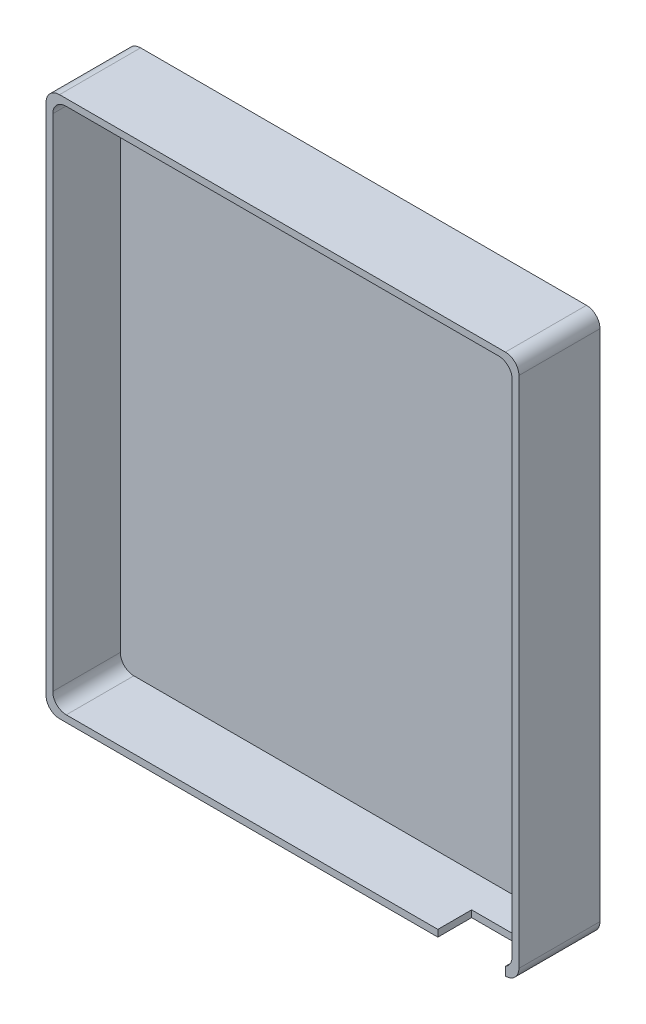
SolidWorks part; units mm, degrees
ref_plane "Front Plane" through (0, 0, 0) normal (0, 0, 1) x (1, 0, 0)
ref_plane "Top Plane" through (0, 0, 0) normal (0, 1, 0) x (1, 0, 0)
ref_plane "Right Plane" through (0, 0, 0) normal (1, 0, 0) x (0, 0, -1)
sketch "Sketch1" plane through (0, 0, 0) normal (0, 0, 1) x (1, 0, 0)
  line L0 (2.54, 0) -> (86.36, 0)
  line L1 (88.9, 2.54) -> (88.9, 99.06)
  line L2 (86.36, 101.6) -> (2.54, 101.6)
  line L3 (0, 99.06) -> (0, 2.54)
  line L8 (3.81, 1.27) -> (85.09, 1.27)
  line L9 (87.63, 3.81) -> (87.63, 97.79)
  line L10 (85.09, 100.33) -> (3.7414, 100.33)
  line L11 (1.27, 97.8586) -> (1.27, 3.81)
  arc A0 (2.54, 101.6) -> (0, 99.06) centre (2.54, 99.06) ccw
  arc A1 (88.9, 99.06) -> (86.36, 101.6) centre (86.36, 99.06) ccw
  arc A2 (86.36, 0) -> (88.9, 2.54) centre (86.36, 2.54) ccw
  arc A3 (0, 2.54) -> (2.54, 0) centre (2.54, 2.54) ccw
  arc A4 (1.27, 3.81) -> (3.81, 1.27) centre (3.81, 3.81) ccw
  arc A5 (85.09, 1.27) -> (87.63, 3.81) centre (85.09, 3.81) ccw
  arc A6 (87.63, 97.79) -> (85.09, 100.33) centre (85.09, 97.79) ccw
  arc A7 (1.27, 97.8586) -> (3.7414, 100.33) centre (3.7414, 97.8586) cw
  point P13 (0, 0)
  dimension "D1" = 2.54
  dimension "D2" = 2.54
  dimension "D3" = 2.54
  dimension "D4" = 2.54
  dimension "D5" = 2.54
  dimension "D6" = 2.54
  dimension "D7" = 2.54
  dimension "D8" = 2.4714
  dimension "D9" = 1.27
  dimension "D10" = 1.27
  dimension "D11" = 88.9
  dimension "D12" = 1.27
  dimension "D13" = 101.6
  dimension "D14" = 1.27
extrude "Boss-Extrude2" add sketch "Sketch1" along normal blind 2.54 contours A7 L11 A4 L8 A5 L9 A6 L10 region at (44.4496, 50.8004, 0)
extrude "Boss-Extrude3" add sketch "Sketch1<3>" along normal blind 15.24 contours L3 A3 L0 A2 L1 A1 L2 A0 L11 A7 L10 A6 L9 A5 L8 A4 region at (1.6986, 1.6986, 0)
sketch "Sketch1<3>" plane through (0, 0, 0) normal (0, 0, 1) x (1, 0, 0) same geometry as "Sketch1"
sketch "Sketch4" plane through (0, 0, 0) normal (0, 0, -1) x (-1, 0, 0)
  line L0 (-88.9, 2.54) -> (-88.9, 99.06) construction
  line L1 (-86.36, 101.6) -> (-2.54, 101.6) construction
  circle A0 centre (-6.35, 6.35) radius 1.016
  circle A1 centre (-6.35, 6.35) radius 1.016
  circle A3 centre (-6.35, 95.25) radius 1.016
  circle A4 centre (-6.35, 95.25) radius 1.7961
  circle A5 centre (-6.35, 6.35) radius 1.7961
  circle A6 centre (-82.55, 95.25) radius 1.016
  circle A7 centre (-82.55, 95.25) radius 1.7961
  circle A8 centre (-82.55, 6.35) radius 1.016
  circle A9 centre (-82.55, 6.35) radius 1.7961
  dimension "D1" = 3.5921
  dimension "D2" = 2.032
  dimension "D3" = 6.35
  dimension "D7" = 2.032
  dimension "D8" = 2.032
  dimension "D9" = 2.032
  dimension "D4" = 6.35
  dimension "D5" = 6.35
  dimension "D6" = 6.35
sketch "Sketch6" plane through (0, 0, 0) normal (0, -1, 0) x (1, 0, 0)
  line L0 (86.36, 15.24) -> (86.36, 8.89)
  line L1 (86.36, 15.24) -> (86.36, 0) construction
  line L3 (73.66, 8.89) -> (73.66, 15.24)
  line L4 (2.54, 15.24) -> (86.36, 15.24) construction
  line L5 (73.66, 15.24) -> (86.36, 15.24)
  line L6 (73.66, 8.89) -> (86.36, 8.89)
extrude "Cut-Extrude3" cut sketch "Sketch6" against normal blind 2.54
sketch "Sketch10" plane through (0, 0, 0) normal (-1, 0, 0) x (0, 0, 1)
  text T0 "OBOY V1.0"
